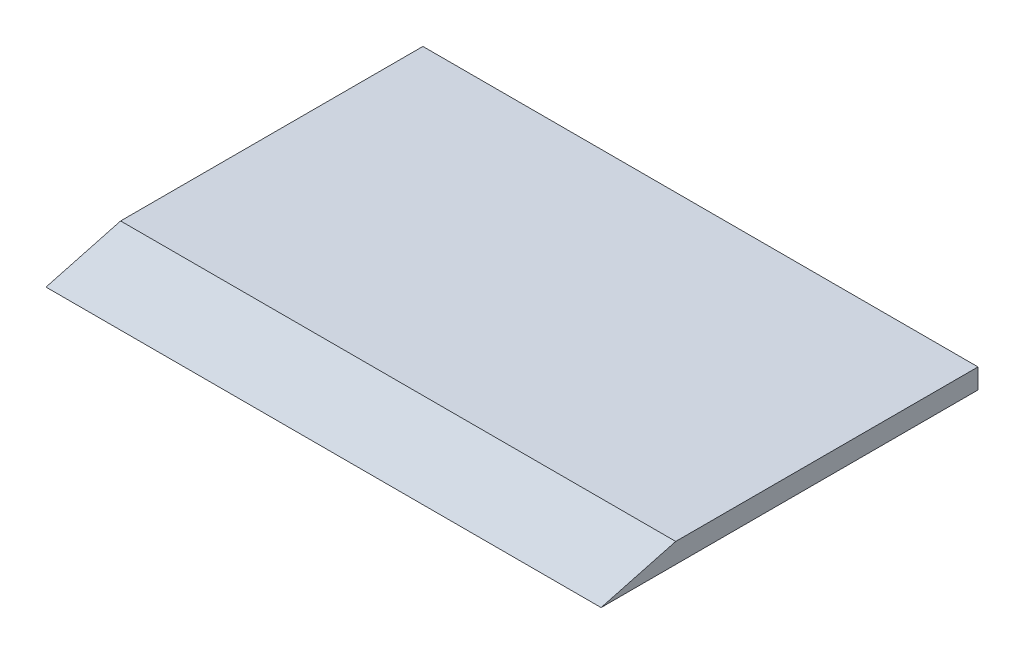
SolidWorks part; units mm, degrees
material "AISI 304"
ref_plane "Front Plane" through (0, 0, 0) normal (0, 0, 1) x (1, 0, 0)
ref_plane "Top Plane" through (0, 0, 0) normal (0, 1, 0) x (1, 0, 0)
ref_plane "Right Plane" through (0, 0, 0) normal (1, 0, 0) x (0, 0, -1)
sketch "Croquis1" plane through (0, 0, 0) normal (1, 0, 0) x (0, 0, -1)
  line L0 (0, 0) -> (67.9, 0)
  line L2 (13.44, 3.6) -> (0, 0)
  line L3 (13.44, 3.6) -> (67.9, 3.6)
  line L4 (67.9, 3.6) -> (67.9, 0)
  dimension "D1" = 14.995
  dimension "D2" = 67.9
  dimension "D3" = 3.6
extrude "Saliente-Extruir1" add sketch "Croquis1" along normal blind 100
